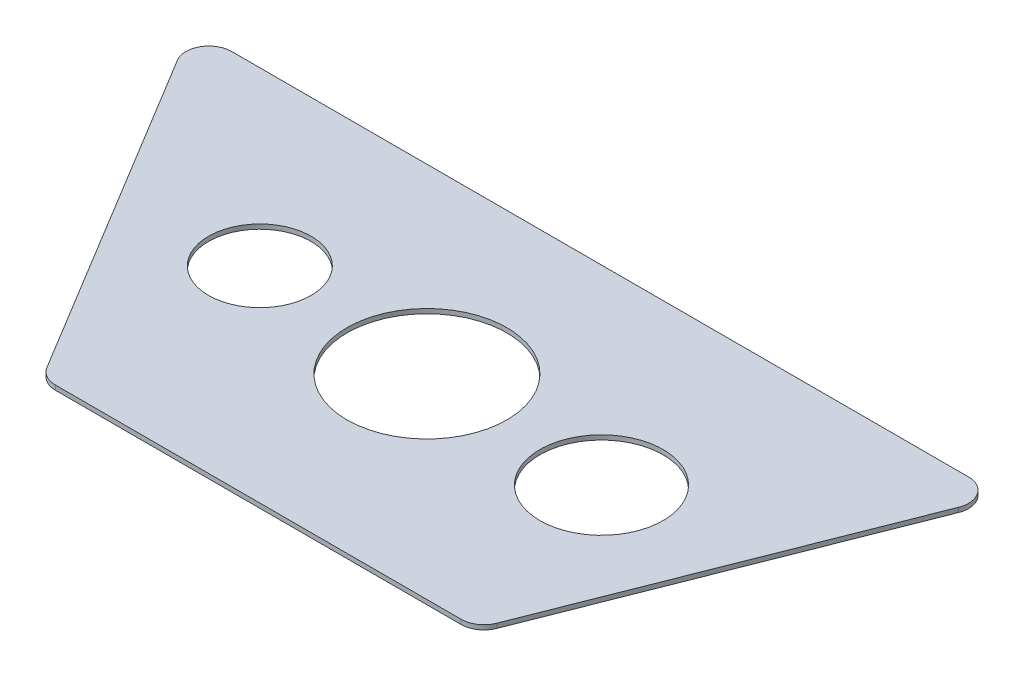
SolidWorks part; units mm, degrees
ref_plane "Front Plane" through (0, 0, 0) normal (0, 0, 1) x (1, 0, 0)
ref_plane "Top Plane" through (0, 0, 0) normal (0, 1, 0) x (1, 0, 0)
ref_plane "Right Plane" through (0, 0, 0) normal (1, 0, 0) x (0, 0, -1)
sketch "Sketch2" plane through (0, 0, 0) normal (0, 1, 0) x (1, 0, 0)
  line L0 (0, 0) -> (65, 165)
  line L1 (65, 165) -> (-290, 165)
  line L2 (-290, 165) -> (-190, 0)
  line L3 (-55, 0) -> (55, 0) construction
  line L4 (-190, 0) -> (0, 0)
  line L5 (0, -55) -> (0, 55) construction
  dimension "D1" = 355
  dimension "D2" = 190
  dimension "D3" = 165
  dimension "D4" = 65
extrude "Boss-Extrude1" add sketch "Sketch2" along normal blind 2
fillet "Fillet1" radius 10 4 edges at (-190, 1, 0) (-290, 1, -165) (65, 1, -165) (0, 1, 0)
sketch "Sketch3" plane through (0, 2, 0) normal (0, 1, 0) x (1, 0, 0)
  circle A0 centre (-184.8365, 89.9232) radius 22.4506
  circle A1 centre (-107.3457, 85.5779) radius 34.9897
  circle A2 centre (-26.958, 81.5947) radius 26.958
extrude "Cut-Extrude1" cut sketch "Sketch3" against normal blind 2
